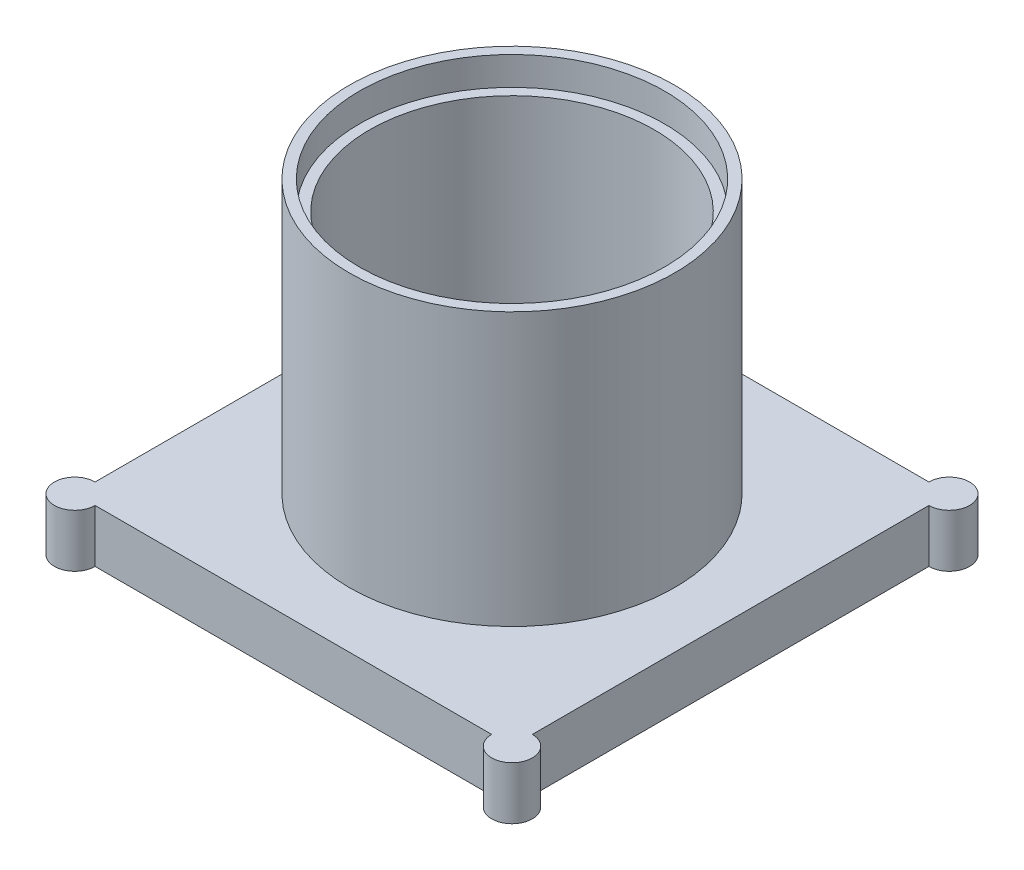
SolidWorks part; units mm, degrees
ref_plane "Ön Düzlem" through (0, 0, 0) normal (0, 0, 1) x (1, 0, 0)
ref_plane "Üst Düzlem" through (0, 0, 0) normal (0, 1, 0) x (1, 0, 0)
ref_plane "Sağ Düzlem" through (0, 0, 0) normal (1, 0, 0) x (0, 0, -1)
sketch "Çizim1" plane through (0, 0, 0) normal (0, 1, 0) x (1, 0, 0)
  line L1 (-96.9134, 75.1697) -> (98.0866, 75.1697)
  line L2 (-106.9134, 65.1697) -> (-106.9134, -129.8303)
  line L3 (-96.9134, -139.8303) -> (98.0866, -139.8303)
  line L4 (108.0866, 65.1697) -> (108.0866, -129.8303)
  line L5 (-106.9134, 75.1697) -> (108.0866, -139.8303) construction
  line L6 (-106.9134, -139.8303) -> (108.0866, 75.1697) construction
  arc A0 (-96.9134, 75.1697) -> (-106.9134, 65.1697) centre (-106.9134, 75.1697) ccw
  arc A1 (-106.9134, -129.8303) -> (-96.9134, -139.8303) centre (-106.9134, -139.8303) ccw
  arc A2 (98.0866, -139.8303) -> (108.0866, -129.8303) centre (108.0866, -139.8303) ccw
  arc A3 (108.0866, 65.1697) -> (98.0866, 75.1697) centre (108.0866, 75.1697) ccw
  circle A4 centre (0.5866, -32.3303) radius 80
  circle A5 centre (0.5866, -32.3303) radius 70
  circle A6 centre (0.5866, -32.3303) radius 75
  point P0 (0.5866, -32.3303)
  point P17 (0, 0)
extrude "Yükseklik-Ekstrüzyon1" add sketch "Çizim1" along normal blind 26 contours L4 A3 L1 A0 L2 A1 L3 A2 A4 region at (0.5866, 0, -71.8463)
extrude "Yükseklik-Ekstrüzyon2" add sketch "Çizim1<7>" along normal blind 160 contours A4 A6 region at (-77.1507, 0, 32.3303)
sketch "Çizim1<7>" plane through (0, 0, 0) normal (0, 1, 0) x (1, 0, 0) same geometry as "Çizim1"
extrude "Yükseklik-Ekstrüzyon3" add sketch "Çizim1<9>" along normal blind 146 contours A6 A5 region at (-72.2921, 0, 32.3303)
sketch "Çizim1<9>" plane through (0, 0, 0) normal (0, 1, 0) x (1, 0, 0) same geometry as "Çizim1"
sketch "Çizim2" plane through (0, 0, 0) normal (0, 1, 0) x (1, 0, 0)
sketch "Çizim3" plane through (0, 0, 0) normal (0, 1, 0) x (1, 0, 0)
sketch "Çizim5" plane through (0, 0, 0) normal (0, -1, 0) x (1, 0, 0)
